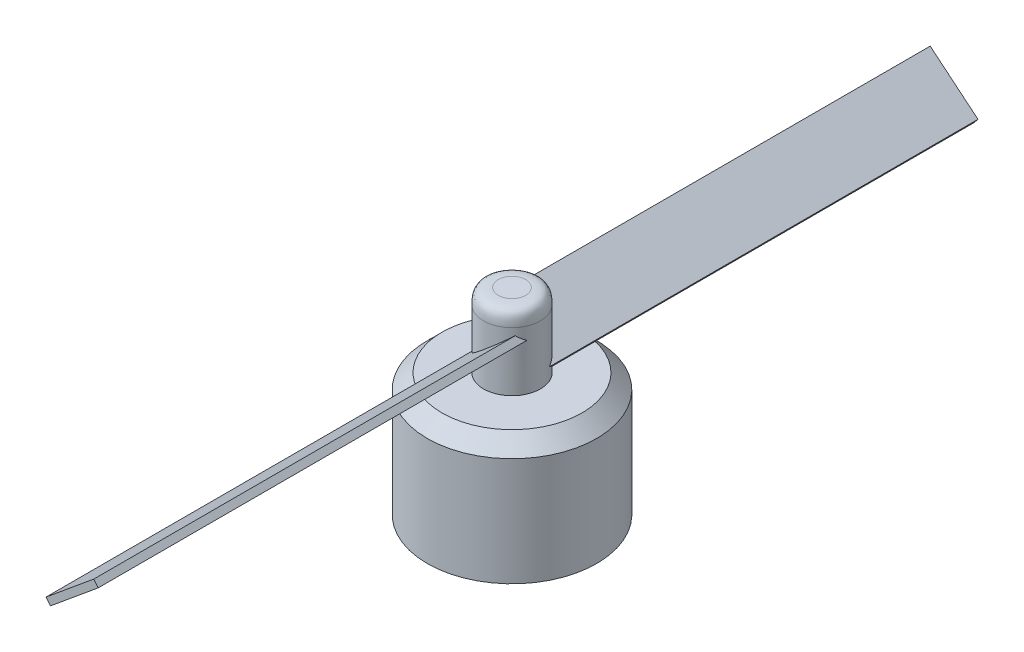
SolidWorks part; units mm, degrees
material "6061-T6 (SS)"
ref_plane "Front Plane" through (0, 0, 0) normal (0, 0, 1) x (1, 0, 0)
ref_plane "Top Plane" through (0, 0, 0) normal (0, 1, 0) x (1, 0, 0)
ref_plane "Right Plane" through (0, 0, 0) normal (1, 0, 0) x (0, 0, -1)
sketch "Sketch1" plane through (0, 0, 0) normal (0, 1, 0) x (1, 0, 0)
  circle A0 centre (0, 0) radius 11.5
  dimension "D1" = 23
extrude "Boss-Extrude1" add sketch "Sketch1" along normal blind 16.7
sketch "Sketch2" plane through (0, 16.7, 0) normal (0, 1, 0) x (1, 0, 0)
  circle A0 centre (0, 0) radius 2.5
  dimension "D1" = 5
extrude "Boss-Extrude2" add sketch "Sketch2" along normal blind 10
chamfer "Chamfer1" distance 2 angle 45 1 edges at (0, 16.7, 11.5)
sketch "Sketch3" plane through (0, 16.7, 0) normal (0, 1, 0) x (1, 0, 0)
  circle A0 centre (0, 0) radius 2.5
  circle A1 centre (0, 0) radius 3.8584
extrude "Boss-Extrude3" add sketch "Sketch3" along normal blind 10
sketch "Sketch4" plane through (0, 0, 0) normal (0, 0, 1) x (1, 0, 0)
  line L0 (-3.5455, 18.3859) -> (2.9397, 23.7469)
  line L1 (-3.5455, 18.3859) -> (-2.9397, 17.6531)
  line L2 (2.9397, 23.7469) -> (3.5455, 23.0141)
  line L3 (-2.9397, 17.6531) -> (3.5455, 23.0141)
  line L4 (-3.5455, 18.3859) -> (3.5455, 23.0141) construction
  line L5 (2.9397, 23.7469) -> (-2.9397, 17.6531) construction
  line L6 (0, 0) -> (0, 28.6962) construction
  line L8 (3.8584, 16.7) -> (-3.8584, 16.7) construction
  point P1 (0, 20.7)
  dimension "D1" = 4
extrude "Boss-Extrude4" add sketch "Sketch4" along normal blind 59.69
pattern_circular "CirPattern1" count 2 over 360 about axis through (0, 0, 0) along (0, 1, 0) of "Boss-Extrude4"
fillet "Fillet2" radius 2 1 edges at (0, 26.7, 3.8584) conic rho 0.6
